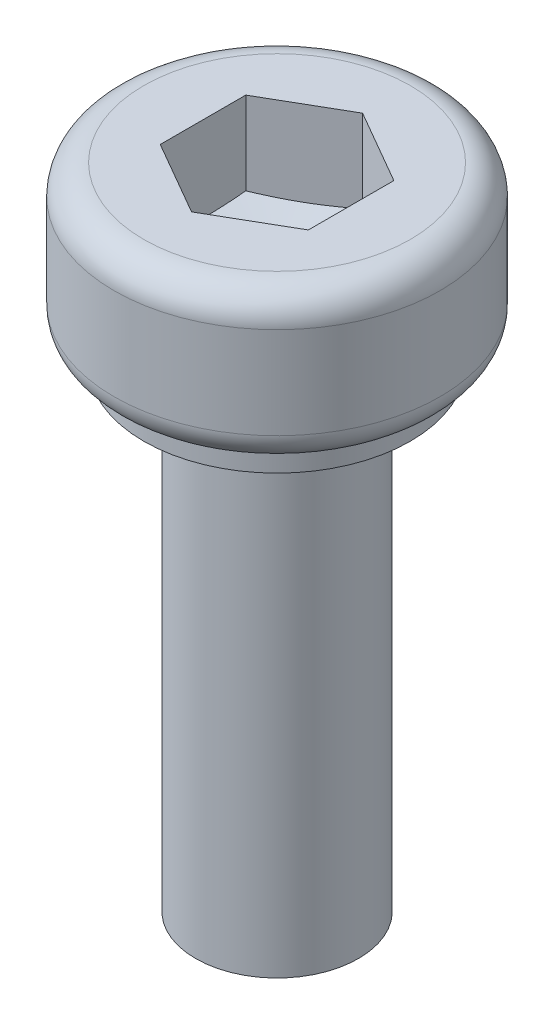
SolidWorks part; units mm, degrees
ref_plane "Front Plane" through (0, 0, 0) normal (0, 0, 1) x (1, 0, 0)
ref_plane "Top Plane" through (0, 0, 0) normal (0, 1, 0) x (1, 0, 0)
ref_plane "Right Plane" through (0, 0, 0) normal (1, 0, 0) x (0, 0, -1)
sketch "Sketch1" plane through (0, 0, 0) normal (0, 0, 1) x (1, 0, 0)
  line L0 (0, 4.0942) -> (0, -5.2249) construction
  line L1 (0, 5.475) -> (2.25, 5.475)
  line L2 (2.75, 4.975) -> (2.75, 3.425)
  line L3 (2.25, 2.525) -> (1.375, 2.525)
  line L4 (1.375, 2.525) -> (1.375, -5.475)
  line L5 (1.375, -5.475) -> (0, -5.475)
  line L6 (0, -5.475) -> (0, 5.475)
  line L7 (2.25, 2.525) -> (2.25, 2.925)
  line L8 (2.75, 2.525) -> (2.25, 2.525) construction
  line L9 (2.75, 3.425) -> (2.75, 2.525) construction
  line L10 (2.75, 5.475) -> (2.75, 4.975) construction
  line L11 (2.25, 5.475) -> (2.75, 5.475) construction
  arc A0 (2.25, 2.925) -> (2.75, 3.425) centre (2.25, 3.425) ccw
  arc A1 (2.25, 5.475) -> (2.75, 4.975) centre (2.25, 4.975) cw
  point P5 (0, 0)
  dimension "D5" = 0.5
  dimension "D1" = 8
  dimension "D2" = 1.375
  dimension "D3" = 2.95
  dimension "D4" = 2.75
  dimension "D6" = 0.4
revolve "Revolve1" add sketch "Sketch1" angle 360 about L0
sketch "Sketch2" plane through (0, 5.475, 0) normal (0, 1, 0) x (1, 0, 0)
  line L1 (0, 1.4434) -> (-1.25, 0.7217)
  line L2 (-1.25, 0.7217) -> (-1.25, -0.7217)
  line L3 (-1.25, -0.7217) -> (0, -1.4434)
  line L4 (0, -1.4434) -> (1.25, -0.7217)
  line L5 (1.25, -0.7217) -> (1.25, 0.7217)
  line L6 (1.25, 0.7217) -> (0, 1.4434)
  circle A0 centre (0, 0) radius 1.25 construction
  dimension "D1" = 2.5
extrude "Boss-Extrude1" add sketch "Sketch2" against normal blind 2 separate body
sketch "Sketch3" plane through (0, 0, 0) normal (1, 0, 0) x (0, 0, -1)
  line L0 (0, 3.875) -> (0.4, 3.875)
  line L1 (0.4, 3.875) -> (1.4434, 4.075)
  line L2 (1.4434, 3.475) -> (1.4434, 5.475) construction
  line L3 (1.4434, 4.075) -> (1.4434, 3.475)
  line L4 (1.4434, 3.475) -> (0, 3.475)
  line L5 (-0.7217, 3.475) -> (0.7217, 3.475) construction
  line L6 (0, 3.475) -> (0, 3.875)
  line L7 (-0.7217, 5.475) -> (0.7217, 5.475) construction
  dimension "D1" = 1.6
  dimension "D2" = 1.4
  dimension "D3" = 0.4
revolve "Cut-Revolve1" cut sketch "Sketch3" angle 360 about L6
combine bodies "Combine1" operation type subtract main body 101 bodies to subtract 104
equation "\"Length\"= 8mm"
equation "\"D1@Sketch1\"=\"Length\""
equation "\"ThreadDiam\"= 2.75"
equation "\"D2@Sketch1\"=\"ThreadDiam\"/2"
equation "\"HeadHeight\"=2.95"
equation "\"D3@Sketch1\"=\"HeadHeight\""
equation "\"HeadDiam\"= 5.5"
equation "\"D4@Sketch1\"=\"HeadDiam\"/2"
equation "\"HexSize\"=2.5"
equation "\"D1@Sketch2\"=\"HexSize\""
